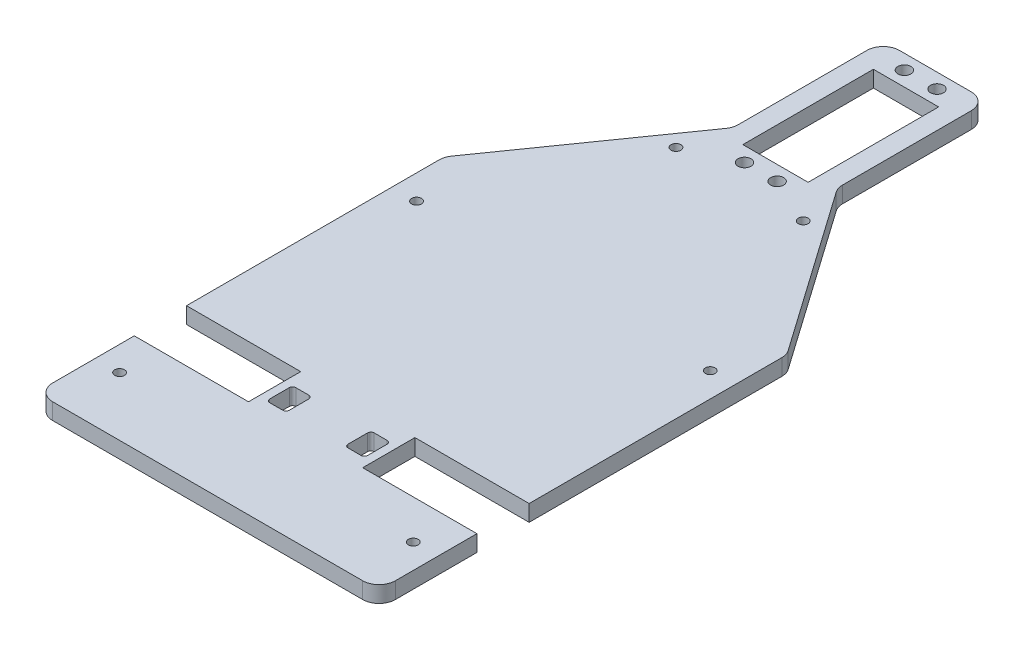
SolidWorks part; units mm, degrees
ref_plane "Front Plane" through (0, 0, 0) normal (0, 0, 1) x (1, 0, 0)
ref_plane "Top Plane" through (0, 0, 0) normal (0, 1, 0) x (1, 0, 0)
ref_plane "Right Plane" through (0, 0, 0) normal (1, 0, 0) x (0, 0, -1)
sketch "Sketch1" plane through (0, 0, 0) normal (0, 1, 0) x (1, 0, 0)
  line L0 (-16, 108) -> (16, 108)
  line L1 (16, 108) -> (16, 62)
  line L2 (16, 62) -> (52.5, 10)
  line L3 (52.5, 10) -> (52.5, -115)
  line L4 (52.5, -115) -> (-52.5, -115)
  line L5 (-52.5, -115) -> (-52.5, 10)
  line L6 (-52.5, 10) -> (-16, 62)
  line L7 (-16, 62) -> (-16, 108)
  dimension "D1" = 52.5
  dimension "D2" = 105
  dimension "D3" = 16
  dimension "D4" = 32
  dimension "D5" = 125
  dimension "D6" = 108
  dimension "D7" = 125
  dimension "D8" = 46
  dimension "D9" = 52
  dimension "D10" = 52
extrude "Boss-Extrude1" add sketch "Sketch1" along normal blind 5
sketch "Sketch2" plane through (0, 5, 0) normal (0, 1, 0) x (1, 0, 0)
  line L5 (-10, 59) -> (-10, 99)
  line L16 (52.5, 10) -> (52.5, -115) construction
  line L17 (-52.5, -69) -> (-17.5, -69)
  line L18 (-52.5, -115) -> (-52.5, 10) construction
  line L19 (-17.5, -69) -> (-17.5, -85)
  line L20 (-17.5, -85) -> (-52.5, -85)
  line L21 (-52.5, -85) -> (-52.5, -69)
  line L22 (17.5, -85) -> (17.5, -69)
  line L23 (17.5, -85) -> (52.5, -85)
  line L24 (17.5, -69) -> (52.5, -69)
  line L25 (52.5, -69) -> (52.5, -85)
  line L27 (52.5, -115) -> (-52.5, -115) construction
  line L29 (-15, -82) -> (-9, -82)
  line L30 (-9, -82) -> (-9, -74)
  line L31 (-15, -74) -> (-9, -74)
  line L32 (-15, -82) -> (-15, -74)
  line L33 (9, -74) -> (9, -82)
  line L34 (9, -82) -> (15, -82)
  line L35 (15, -82) -> (15, -74)
  line L36 (15, -74) -> (9, -74)
  line L37 (-16, 108) -> (16, 108) construction
  line L38 (-16, 62) -> (-16, 108) construction
  line L40 (-10, 99) -> (10, 99)
  line L41 (10, 99) -> (10, 59)
  line L42 (10, 59) -> (-10, 59)
  circle A0 centre (-5, 103.5) radius 2
  circle A1 centre (5, 103.5) radius 2
  circle A2 centre (-5, 54.5) radius 2
  circle A3 centre (5, 54.5) radius 2
  circle A6 centre (-19.5, 48) radius 1.5
  circle A7 centre (19.5, 48) radius 1.5
  circle A8 centre (45, -6) radius 1.5
  circle A9 centre (-45, -6) radius 1.5
  circle A10 centre (45, -97) radius 1.5
  circle A11 centre (-45, -97) radius 1.5
  dimension "D5" = 4
  dimension "D8" = 4
  dimension "D11" = 4
  dimension "D14" = 40
  dimension "D21" = 91
  dimension "D24" = 16
  dimension "D27" = 3
  dimension "D30" = 3
  dimension "D37" = 3
  dimension "D38" = 3
  dimension "D39" = 3
  dimension "D40" = 3
  dimension "D26" = 4
  dimension "D7" = 4.5
  dimension "D9" = 20
  dimension "D10" = 4.5
  dimension "D12" = 6
  dimension "D13" = 11
  dimension "D15" = 49
  dimension "D16" = 49
  dimension "D17" = 11
  dimension "D18" = 60
  dimension "D19" = 60
  dimension "D20" = 7.5
  dimension "D22" = 91
  dimension "D23" = 33
  dimension "D25" = 16
  dimension "D28" = 33
  dimension "D33" = 7.5
  dimension "D35" = 7.5
  dimension "D41" = 7.5
  dimension "D42" = 4.5
  dimension "D44" = 5
  dimension "D45" = 5
  dimension "D49" = 35
  dimension "D50" = 16
  dimension "D51" = 30
  dimension "D52" = 16
  dimension "D53" = 35
  dimension "D54" = 30
  dimension "D55" = 8
  dimension "D56" = 6
  dimension "D57" = 2.5
  dimension "D58" = 5
  dimension "D59" = 8
  dimension "D60" = 6
  dimension "D61" = 2.5
  dimension "D62" = 5
extrude "Cut-Extrude1" cut sketch "Sketch2" against normal blind 7
fillet "Fillet1" radius 5 1 edges at (16, 2.5, -108)
fillet "Fillet2" radius 5 1 edges at (-16, 2.5, -108)
fillet "Fillet3" radius 5 1 edges at (52.5, 2.5, -10)
fillet "Fillet4" radius 5 1 edges at (-52.5, 2.5, -10)
fillet "Fillet5" radius 5 1 edges at (52.5, 2.5, 115)
fillet "Fillet6" radius 5 1 edges at (-52.5, 2.5, 115)
fillet "Fillet8" radius 1 1 edges at (15, 2.5, 74)
fillet "Fillet9" radius 1 7 edges at (-15, 2.5, 82) (-15, 2.5, 74) (-9, 2.5, 82) (-9, 2.5, 74) (9, 2.5, 82) (15, 2.5, 82) (9, 2.5, 74)
fillet "Fillet10" radius 5 2 edges at (-16, 2.5, -62) (16, 2.5, -62)
